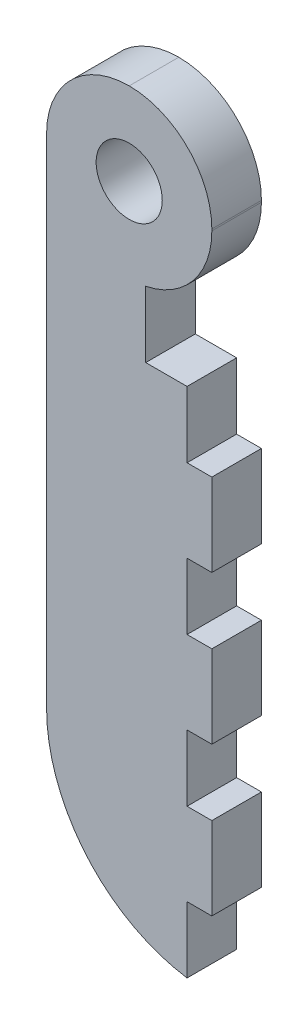
SolidWorks part; units mm, degrees
ref_plane "Plan de face" through (0, 0, 0) normal (0, 0, 1) x (1, 0, 0)
ref_plane "Plan de dessus" through (0, 0, 0) normal (0, 1, 0) x (1, 0, 0)
ref_plane "Plan de droite" through (0, 0, 0) normal (1, 0, 0) x (0, 0, -1)
sketch "Esquisse1" plane through (0, 0, 0) normal (0, 0, 1) x (1, 0, 0)
  line L0 (-3, 54) -> (-3, 44)
  line L1 (0, 0) -> (-20, 0)
  line L2 (0, 0) -> (0, 90)
  line L3 (0, 90) -> (-20, 90)
  line L4 (-20, 0) -> (-20, 90)
  line L5 (0, 0) -> (-3, 0)
  line L6 (0, 0) -> (0, 8)
  line L7 (0, 8) -> (-3, 8)
  line L8 (-3, 0) -> (-3, 8)
  line L9 (0, 18) -> (-3, 18)
  line L10 (0, 18) -> (0, 26)
  line L11 (0, 26) -> (-3, 26)
  line L12 (-3, 18) -> (-3, 26)
  line L13 (0, 36) -> (-3, 36)
  line L14 (0, 36) -> (0, 44)
  line L15 (0, 44) -> (-3, 44)
  line L16 (-3, 36) -> (-3, 44)
  line L17 (0, 54) -> (-3, 54)
  line L18 (0, 54) -> (0, 62)
  line L19 (0, 62) -> (-3, 62)
  line L20 (-3, 54) -> (-3, 62)
  line L21 (-3, 36) -> (-3, 26)
  line L22 (-3, 18) -> (-3, 8)
  circle A0 centre (-10, 80) radius 4
  dimension "D3" = 10
  dimension "D7" = 8
  dimension "D1" = 20
  dimension "D2" = 90
  dimension "D4" = 10
  dimension "D5" = 8
  dimension "D6" = 10
  dimension "D8" = 3
extrude "Boss.-Extru.1" add sketch "Esquisse1" along normal blind 6 contours L22 L12 L21 L16 L0 L20 L19 L2 L3 L4 L1 L8 A0 | L2 L17 L0 L15 | L13 L21 L11 L2 | L9 L22 L7 L2 region at (-1.5, 49, 0) region at (-11.011, 45.5402, 0) region at (-1.5, 31, 0) region at (-1.5, 13, 0)
sketch "Esquisse2" plane through (0, 0, 6) normal (0, 0, 1) x (1, 0, 0)
  line L0 (-3, 62) -> (-8, 62)
  line L1 (-8, 62) -> (-8, 70)
  line L2 (-8, 70) -> (0, 70)
  line L3 (0, 62) -> (0, 90) construction
  line L4 (0, 70) -> (0, 62)
  line L5 (0, 62) -> (-3, 62)
  dimension "D1" = 8
  dimension "D2" = 8
extrude "Enlèv. mat.-Extru.1" cut sketch "Esquisse2" against normal blind 6
fillet "Congé1" radius 10 3 edges at (-20, 90, 3) (0, 70, 3) (0, 90, 3)
fillet "Congé2" radius 20 1 edges at (-20, 0, 3)
